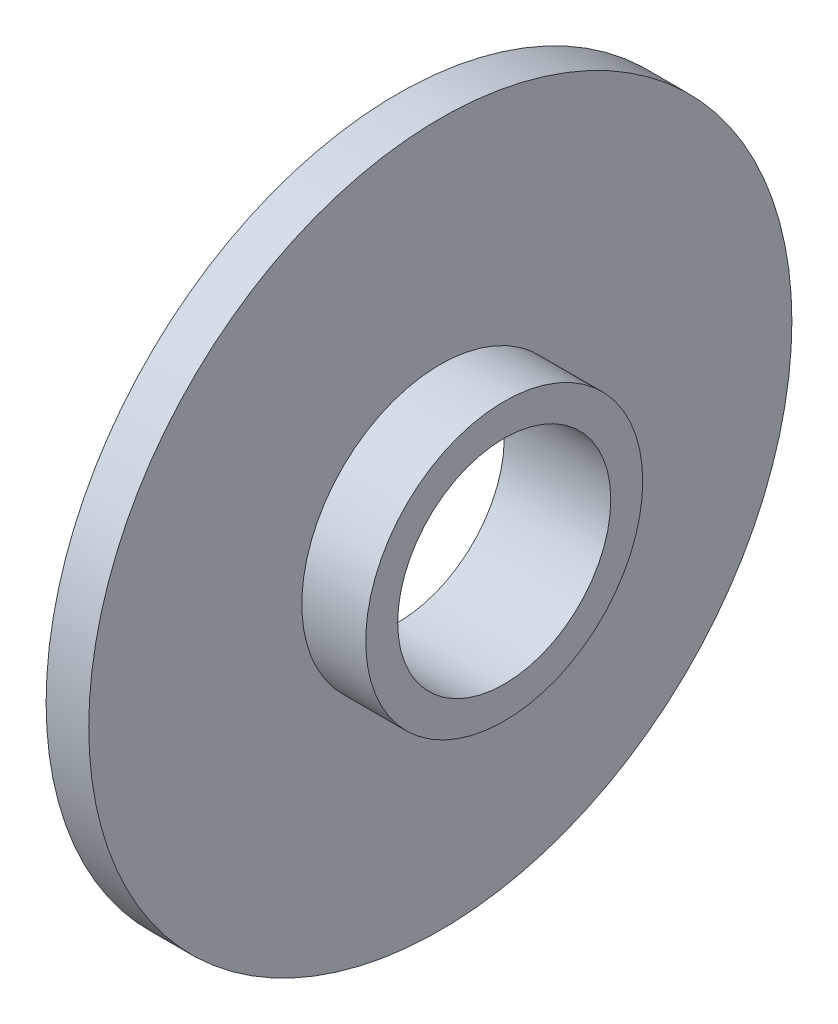
SolidWorks part; units mm, degrees
ref_plane "Front Plane" through (0, 0, 0) normal (0, 0, 1) x (1, 0, 0)
ref_plane "Top Plane" through (0, 0, 0) normal (0, 1, 0) x (1, 0, 0)
ref_plane "Right Plane" through (0, 0, 0) normal (1, 0, 0) x (0, 0, -1)
ref_axis "X-Axis" through (88.99, 0, 0) along (-1, 0, 0)
ref_axis "Y-Axis" through (0, 0, -88.99) along (0, 0, 1)
ref_axis "Z-Axis" through (0, -55, 0) along (0, 1, 0)
sketch "Sketch1" plane through (0, 0, 0) normal (0, 1, 0) x (1, 0, 0)
  line L0 (88.99, 0) -> (-88.99, 0) construction
  line L1 (-1, 16.5) -> (1, 16.5)
  line L2 (-1, 16.5) -> (-1, 5)
  line L4 (1, 16.5) -> (1, 6.5)
  line L5 (-1, 5) -> (4, 5)
  line L7 (1, 6.5) -> (4, 6.5)
  line L8 (4, 5) -> (4, 6.5)
  line L9 (0, 88.99) -> (0, -88.99) construction
  point P1 (0, 16.5)
  dimension "D1" = 6.5
  dimension "D2" = 1.5
  dimension "D3" = 10
  dimension "D4" = 2
  dimension "D5" = 3
revolve "Revolve1" add sketch "Sketch1" angle 360 about axis through (88.99, 0, 0) along (-1, 0, 0)
